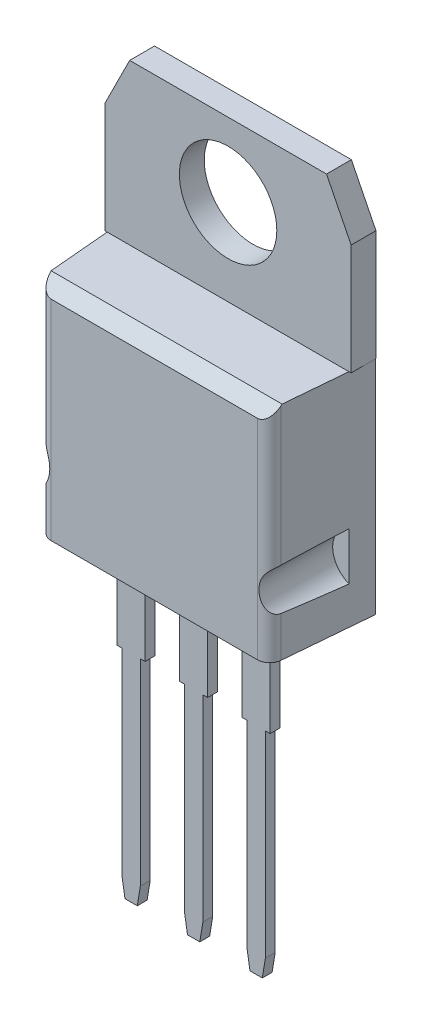
SolidWorks part; units mm, degrees
ref_plane "Front Plane" through (0, 0, 0) normal (0, 0, 1) x (1, 0, 0)
ref_plane "Top Plane" through (0, 0, 0) normal (0, 1, 0) x (1, 0, 0)
ref_plane "Right Plane" through (0, 0, 0) normal (1, 0, 0) x (0, 0, -1)
sketch "Sketch2" plane through (0, 0, 0) normal (0, 0, 1) x (1, 0, 0)
  line L1 (-5, -4.5) -> (5, -4.5)
  line L2 (-5, -4.5) -> (-5, 4.5)
  line L3 (-5, 4.5) -> (5, 4.5)
  line L4 (5, -4.5) -> (5, 4.5)
  line L5 (-5, -4.5) -> (5, 4.5) construction
  line L6 (-5, 4.5) -> (5, -4.5) construction
  point P0 (0, 0)
  dimension "D1" = 10
  dimension "D2" = 9
extrude "Boss-Extrude1" add sketch "Sketch2" along normal blind 4
chamfer "Chamfer1" distance 0.5 angle 45 1 edges at (0, 4.5, 4)
sketch "Sketch6" plane through (0, 0, 4) normal (0, 0, 1) x (1, 0, 0)
  line L0 (5, -4.5) -> (5, 4) construction
  line L1 (-5, -4.5) -> (5, -4.5) construction
  line L2 (5, -1) -> (5, -3)
  arc A0 (5, -3) -> (5, -1) centre (5.2917, -2) cw
  point P7 (4.25, -2)
  dimension "D1" = 1.5
  dimension "D2" = 2
  dimension "D3" = 0.75
extrude "Cut-Extrude1" cut sketch "Sketch6" against normal blind 3 contours A0 L2
mirror "Mirror1" about plane through (0, 0, 0) normal (1, 0, 0) of "Cut-Extrude1"
ref_plane "Plane1" through (0, 0, 2) normal (0, 0, 1) x (1, 0, 0)
sketch "Sketch7" plane through (0, 0, 2) normal (0, 0, 1) x (1, 0, 0)
  line L0 (-0.57, -4.5) -> (-0.57, -8.44)
  line L1 (-5, -4.5) -> (5, -4.5) construction
  line L2 (-0.57, -8.44) -> (-0.375, -8.44)
  line L3 (-0.375, -8.44) -> (-0.375, -16.44)
  line L4 (-0.375, -16.44) -> (-0.25, -17.2)
  line L5 (-0.25, -17.2) -> (0.25, -17.2)
  line L6 (0.25, -17.2) -> (0.375, -16.44)
  line L7 (0.375, -16.44) -> (0.375, -8.44)
  line L8 (0.375, -8.44) -> (0.57, -8.44)
  line L9 (0.57, -8.44) -> (0.57, -4.5)
  line L10 (0.57, -4.5) -> (-0.57, -4.5)
  point P5 (0, -17.2)
  dimension "D1" = 3.94
  dimension "D2" = 8.76
  dimension "D3" = 1.14
  dimension "D4" = 0.75
  dimension "D5" = 8
  dimension "D6" = 0.5
  dimension "D7" = 0.57
extrude "Boss-Extrude2" add sketch "Sketch7" along normal blind 0.4 contours L0 L2 L3 L4 L5 L6 L7 L8 L9 L10
pattern_linear "LPattern1" count 2 spacing 2.54 along (-1, 0, 0) of "Boss-Extrude2"
pattern_linear "LPattern2" count 2 spacing 2.54 along (1, 0, 0) of "Boss-Extrude2"
draft "Draft2" type of draft neutral plane draft angle 5 faces to draft 2 face at (5, -0.4444, 2.3889) face at (-5, -0.4444, 2.3889) neutral plane through (0, 0, 0) neutral plane normal (0, 0, -1) reverse direction yes parameters "D1"=5
sketch "Sketch8" plane through (0, 0, 0) normal (0, 0, -1) x (-1, 0, 0)
  line L0 (-5, 9) -> (-4, 11)
  line L1 (-5, 4.5) -> (5, 4.5)
  line L2 (-5, 4.5) -> (-5, 9)
  line L3 (-4, 11) -> (4, 11)
  line L4 (5, 4.5) -> (5, 9)
  line L5 (4, 11) -> (5, 9)
  circle A0 centre (0, 8) radius 1.98
  point P1 (5, 11)
  point P2 (-5, 11)
  dimension "D7" = 3.96
  dimension "D1" = 6.5
  dimension "D2" = 10
  dimension "D3" = 2
  dimension "D4" = 1
  dimension "D5" = 1
  dimension "D6" = 2
  dimension "D8" = 3
extrude "Boss-Extrude3" add sketch "Sketch8" against normal blind 1 and the other way blind 0.01
fillet "Fillet1" radius 0.5 2 edges at (-4.65, 1.4103, 4) (4.65, 1.4103, 4)
